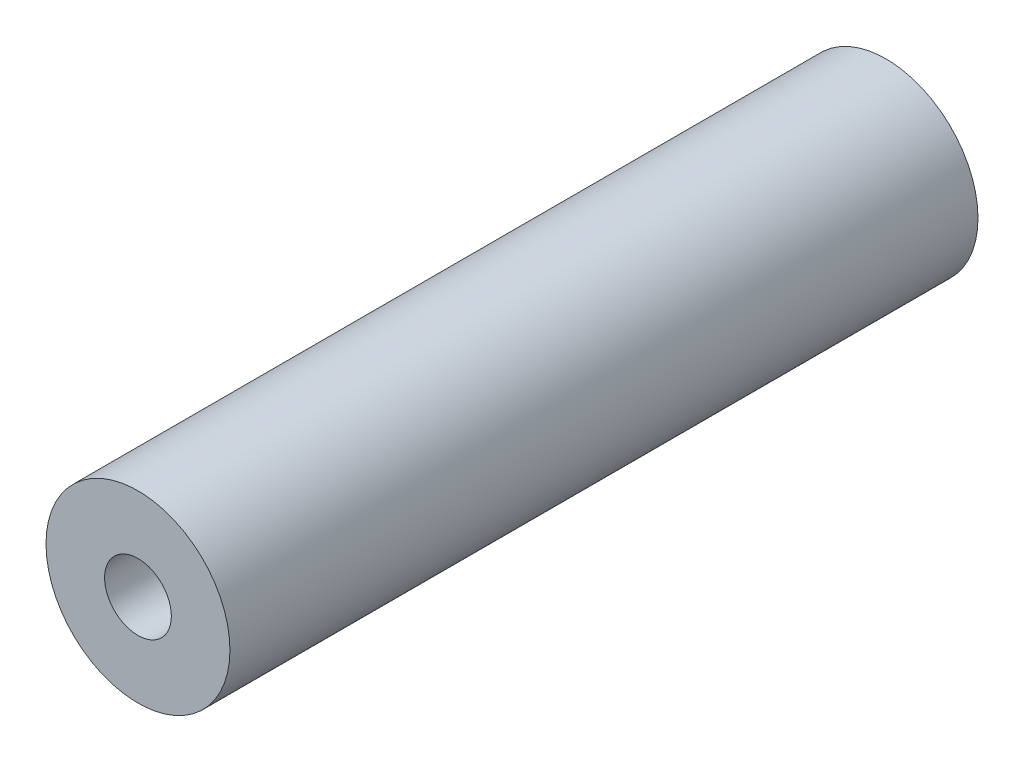
SolidWorks part; units mm, degrees
material "PET"
ref_plane "Front Plane" through (0, 0, 0) normal (0, 0, 1) x (1, 0, 0)
ref_plane "Top Plane" through (0, 0, 0) normal (0, 1, 0) x (1, 0, 0)
ref_plane "Right Plane" through (0, 0, 0) normal (1, 0, 0) x (0, 0, -1)
ref_axis "X AXIS" through (-88.99, 0, 0) along (1, 0, 0)
ref_axis "Y AXIS" through (0, 55, 0) along (0, -1, 0)
ref_axis "Z AXIS" through (0, 0, -88.99) along (0, 0, 1)
sketch "Sketch1" plane through (0, 0, 0) normal (1, 0, 0) x (0, 0, -1)
  line L0 (0, 0) -> (-26.6258, 0) construction
  line L1 (0, 0) -> (38.735, 0)
  line L2 (0, 0) -> (0, 4.7625)
  line L3 (0, 4.7625) -> (38.735, 4.7625)
  line L4 (38.735, 0) -> (38.735, 4.7625)
  line L5 (88.99, 0) -> (-88.99, 0) construction
  dimension "D1" = 38.735
  dimension "D2" = 9.525
revolve "Revolve1" add sketch "Sketch1" angle 360 about L0
hole_wizard "#8-32 Tapped Hole1" positions "Sketch2" profile "Sketch3" tap size "#8-32" standard "ANSI Inch"
sketch "Sketch2" plane through (0, 0, 0) normal (0, 0, 1) x (1, 0, 0)
  point P0 (0, 0)
  point P3 (0, 0)
sketch "Sketch3" plane through (0, 0, 0) normal (1, 0, 0) x (0, -1, 0)
  line L0 (0, 0) -> (0, 11.7566)
  line L1 (0, 11.7566) -> (1.7272, 10.7188)
  line L2 (1.7272, 10.7188) -> (1.7272, 0)
  line L5 (1.7272, 0) -> (0, 0)
  line L10 (0, 11.7566) -> (-1.7272, 10.7188) construction
  line L11 (0, -6.35) -> (0, 107.95) construction
  dimension "Tap Drill Dia." = 3.4544
  dimension "Tap Drill Depth" = 10.7188
  dimension "Drill Angle" = 118
cosmetic thread "Hole Thread1" parameters "D1"=8.3312, "D2"=4.1656
hole_wizard "#8-32 Tapped Hole2" positions "Sketch4" profile "Sketch5" tap size "#8-32" standard "ANSI Inch"
sketch "Sketch4" plane through (0, 0, -38.735) normal (0, 0, -1) x (-1, 0, 0)
  point P0 (0, 0)
sketch "Sketch5" plane through (0, 0, -38.735) normal (1, 0, 0) x (0, 1, 0)
  line L0 (0, 0) -> (0, 11.7566)
  line L1 (0, 11.7566) -> (1.7272, 10.7188)
  line L2 (1.7272, 10.7188) -> (1.7272, 0)
  line L5 (1.7272, 0) -> (0, 0)
  line L10 (0, 11.7566) -> (-1.7272, 10.7188) construction
  line L11 (0, -6.35) -> (0, 107.95) construction
  dimension "Tap Drill Dia." = 3.4544
  dimension "Tap Drill Depth" = 10.7188
  dimension "Drill Angle" = 118
cosmetic thread "Hole Thread2" parameters "D1"=8.3312, "D2"=4.1656
